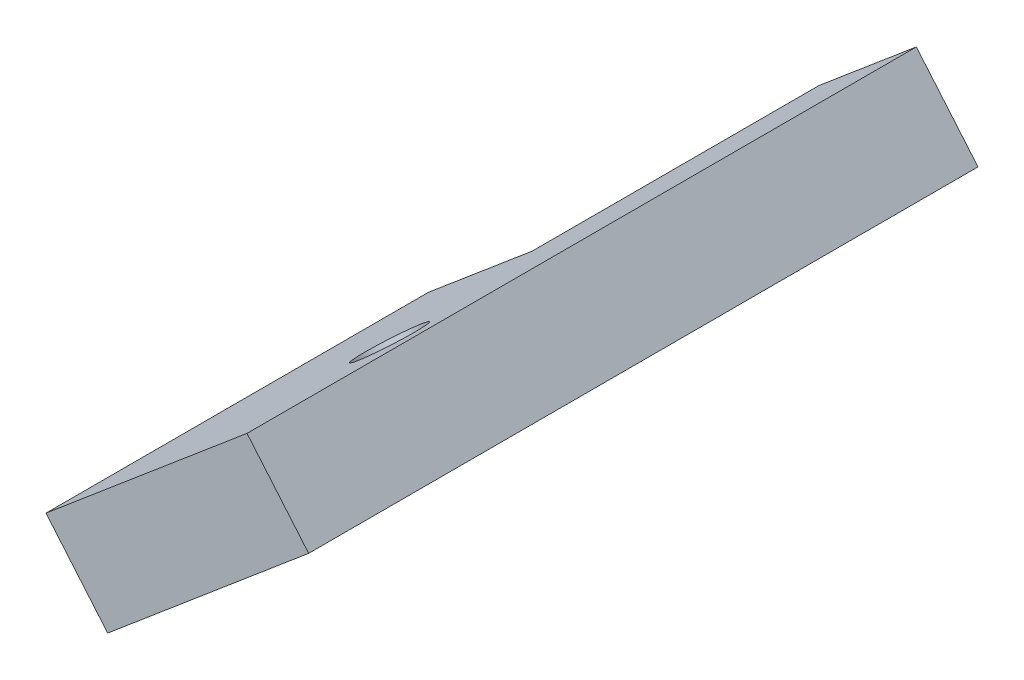
SolidWorks part; units mm, degrees
ref_plane "Front Plane" through (0, 0, 0) normal (0, 0, 1) x (1, 0, 0)
ref_plane "Top Plane" through (0, 0, 0) normal (0, 1, 0) x (1, 0, 0)
ref_plane "Right Plane" through (0, 0, 0) normal (1, 0, 0) x (0, 0, -1)
sketch "Sketch4" plane through (454.1451, -538.3327, 0) normal (0.6448, -0.7643, 0) x (0.7643, 0.6448, 0)
  line L1 (554.952, 0) -> (554.952, 12)
  line L2 (554.952, 12) -> (546.702, 12)
  line L3 (546.702, 12) -> (546.702, 0)
  line L4 (546.702, 0) -> (550.952, 0)
  line L5 (550.952, 0) -> (550.952, -9)
  line L6 (550.952, -9) -> (554.952, -9)
  line L7 (554.952, -9) -> (550.952, -9) construction
  line L8 (554.952, -9) -> (554.952, 0)
  line L9 (554.952, -9) -> (554.952, 0) construction
  circle A0 centre (552.952, 6) radius 1
  point P1 (547.4153, 0)
  point P7 (0, 0)
  point P13 (554.5582, 0)
  point P15 (546.702, 0)
  dimension "D1" = 2
  dimension "D2" = 2
  dimension "D3" = 6
  dimension "D4" = 6
extrude "Boss-Extrude1" add sketch "Sketch4" along normal up to surface (3 mm away)
